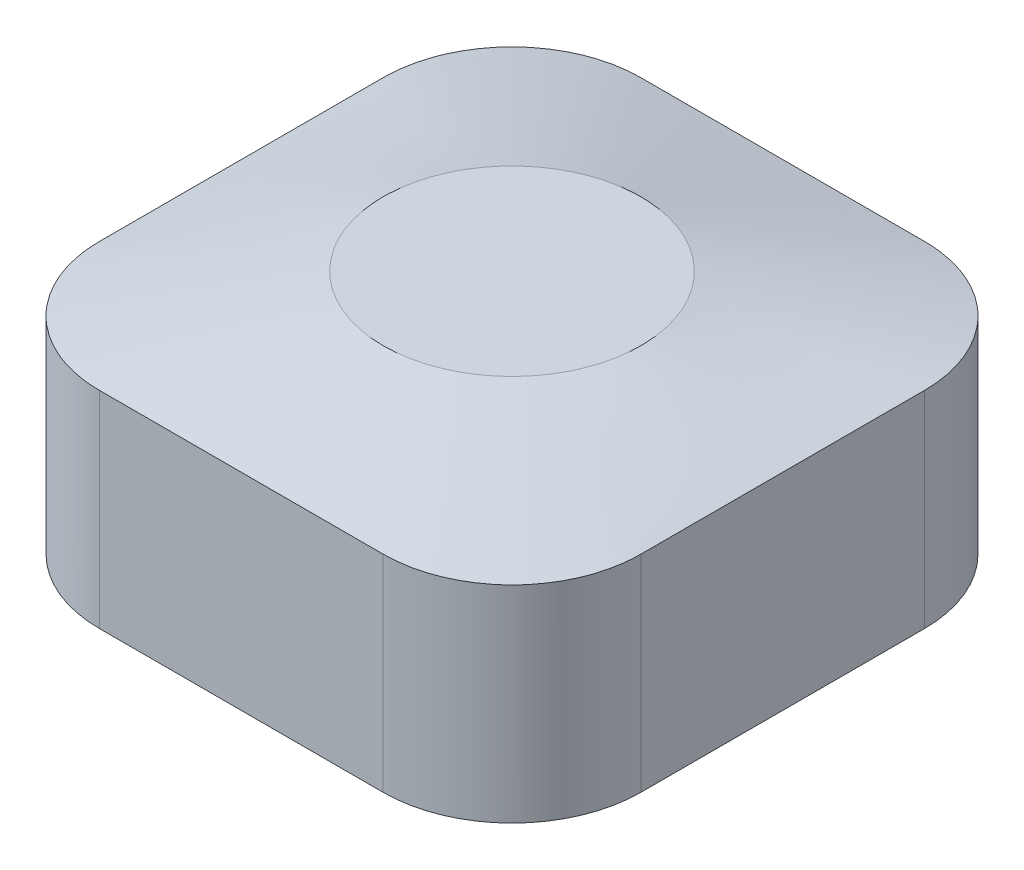
SolidWorks part; units mm, degrees
ref_plane "Front Plane" through (0, 0, 0) normal (0, 0, 1) x (1, 0, 0)
ref_plane "Top Plane" through (0, 0, 0) normal (0, 1, 0) x (1, 0, 0)
ref_plane "Right Plane" through (0, 0, 0) normal (1, 0, 0) x (0, 0, -1)
sketch "Sketch1" plane through (0, 0, 0) normal (0, 1, 0) x (1, 0, 0)
  line L0 (0, 0) -> (21, 0)
  line L1 (21, 0) -> (21, -21)
  line L2 (21, -21) -> (0, -21)
  line L3 (0, -21) -> (0, 0)
  dimension "D1" = 21
  dimension "D2" = 21
extrude "Boss-Extrude1" add sketch "Sketch1" along normal blind 8
fillet "Fillet1" radius 5 4 edges at (0, 4, 0) (21, 4, 0) (21, 4, 21) (0, 4, 21)
ref_plane "Plane1" through (0, 8, 0) normal (0, 1, 0) x (1, 0, 0)
ref_plane "Plane2" through (0, 9.5, 0) normal (0, 1, 0) x (1, 0, 0)
sketch "Sketch2" plane through (0, 9.5, 0) normal (0, 1, 0) x (1, 0, 0)
  line L0 (0, -5) -> (0, -16) construction
  line L3 (16, 0) -> (5, 0) construction
  circle A0 centre (10.5, -10.5) radius 5
  point P5 (0, -10.5)
  point P8 (10.5, 0)
  dimension "D1" = 10
sketch "Sketch10" plane through (0, 0, 0) normal (0, -1, 0) x (1, 0, 0)
  line L0 (5, 21) -> (16, 21) construction
  line L1 (5, 1.5) -> (16, 1.5)
  line L2 (1.5, 5) -> (1.5, 16)
  line L3 (5, 19.5) -> (16, 19.5)
  line L4 (19.5, 5) -> (19.5, 16)
  line L5 (1.5, 1.5) -> (19.5, 19.5) construction
  line L6 (1.5, 19.5) -> (19.5, 1.5) construction
  line L7 (21, 16) -> (21, 5) construction
  line L8 (16, 0) -> (5, 0) construction
  line L9 (0, 5) -> (0, 16) construction
  arc A0 (5, 1.5) -> (1.5, 5) centre (5, 5) cw
  arc A1 (16, 1.5) -> (19.5, 5) centre (16, 5) ccw
  arc A2 (16, 19.5) -> (19.5, 16) centre (16, 16) cw
  arc A3 (5, 19.5) -> (1.5, 16) centre (5, 16) ccw
  point P0 (10.5, 10.5)
  dimension "D5" = 3.5
  dimension "D1" = 1.5
  dimension "D2" = 1.5
  dimension "D3" = 1.5
  dimension "D4" = 1.5
extrude "Cut-Extrude2" cut sketch "Sketch10" against normal blind 6.5
sketch "Sketch11" plane through (0, 6.5, 0) normal (0, -1, 0) x (1, 0, 0)
  line L0 (5, 21) -> (16, 21) construction
  line L1 (21, 16) -> (21, 5) construction
  circle A0 centre (10.5, 10.5) radius 2.65
  dimension "D3" = 5.3
  dimension "D1" = 10.5
  dimension "D2" = 10.5
extrude "Boss-Extrude4" add sketch "Sketch11" along normal blind 3
sketch "Sketch3" plane through (0, 8, 0) normal (0, 1, 0) x (1, 0, 0)
  line L0 (16, 0) -> (5, 0) construction
  line L1 (16, 0) -> (5, 0)
  line L2 (21, -16) -> (21, -5) construction
  line L3 (5, -21) -> (16, -21) construction
  line L4 (0, -5) -> (0, -16) construction
  line L5 (21, -16) -> (21, -5)
  line L6 (5, -21) -> (16, -21)
  line L7 (0, -5) -> (0, -16)
  arc A0 (21, -5) -> (16, 0) centre (16, -5) ccw construction
  arc A1 (16, -21) -> (21, -16) centre (16, -16) ccw construction
  arc A2 (0, -16) -> (5, -21) centre (5, -16) ccw construction
  arc A3 (5, 0) -> (0, -5) centre (5, -5) ccw construction
  arc A4 (21, -5) -> (16, 0) centre (16, -5) ccw
  arc A5 (16, -21) -> (21, -16) centre (16, -16) ccw
  arc A6 (0, -16) -> (5, -21) centre (5, -16) ccw
  arc A7 (5, 0) -> (0, -5) centre (5, -5) ccw
loft "Loft2" add profiles "Sketch3", "Sketch2"
